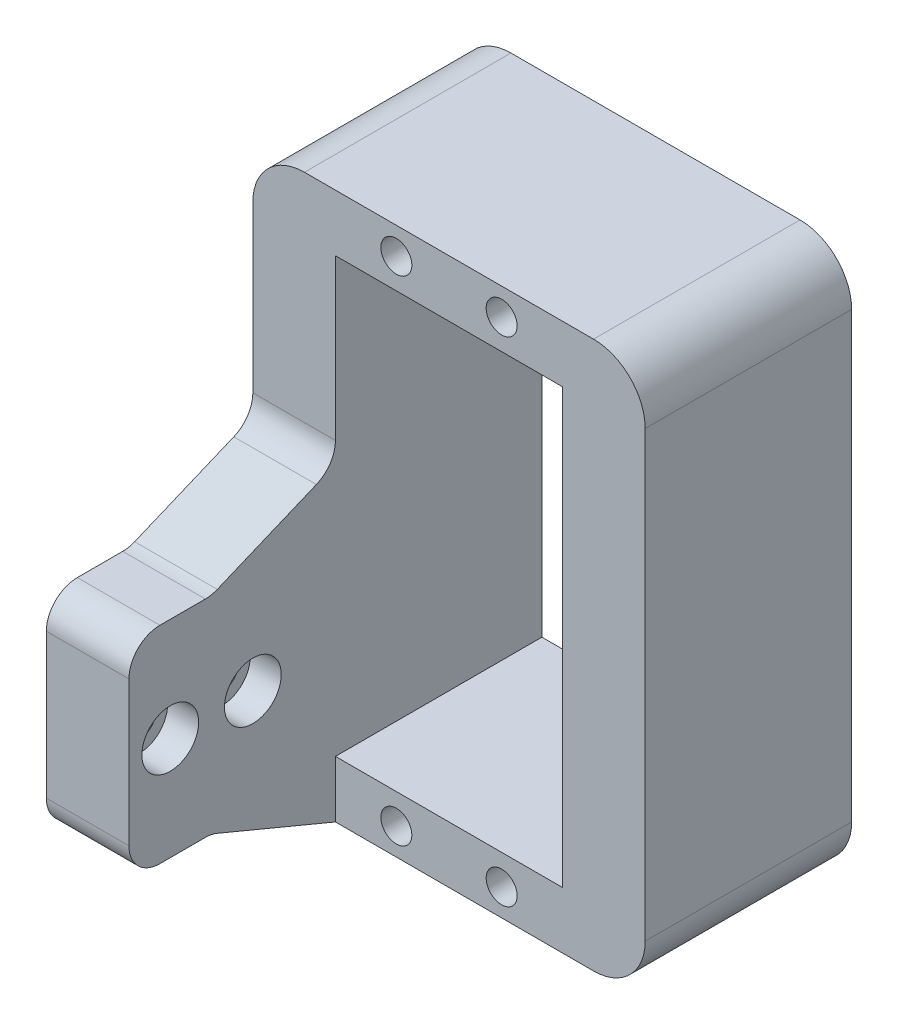
SolidWorks part; units mm, degrees
ref_plane "Front Plane" through (0, 0, 0) normal (0, 0, 1) x (1, 0, 0)
ref_plane "Top Plane" through (0, 0, 0) normal (0, 1, 0) x (1, 0, 0)
ref_plane "Right Plane" through (0, 0, 0) normal (1, 0, 0) x (0, 0, -1)
sketch "Sketch1" plane through (0, 0, 0) normal (0, 0, 1) x (1, 0, 0)
  line L1 (-11, 21) -> (11, 21)
  line L2 (-11, 21) -> (-11, -21)
  line L3 (-11, -21) -> (11, -21)
  line L4 (11, 21) -> (11, -21)
  line L5 (-11, 21) -> (11, -21) construction
  line L6 (-11, -21) -> (11, 21) construction
  line L8 (-19, 26.5) -> (19, 26.5)
  line L9 (-19, 26.5) -> (-19, -26.5)
  line L10 (-19, -26.5) -> (19, -26.5)
  line L11 (19, 26.5) -> (19, -26.5)
  line L12 (-19, 26.5) -> (19, -26.5) construction
  line L13 (-19, -26.5) -> (19, 26.5) construction
  point P0 (0, 0)
  point P6 (0, 0)
  dimension "D1" = 22
  dimension "D2" = 42
  dimension "D4" = 8
  dimension "D3" = 53
extrude "Boss-Extrude1" add sketch "Sketch1" along normal blind 20
sketch "Sketch2" plane through (0, 0, 20) normal (0, 0, 1) x (1, 0, 0)
  line L0 (-19, 26.5) -> (-19, -26.5) construction
  line L1 (-19, -21.5) -> (-11, -21.5)
  line L2 (-19, -21.5) -> (-19, -1.5)
  line L3 (-19, -1.5) -> (-11, -1.5)
  line L4 (-11, -21.5) -> (-11, -1.5)
  line L5 (-11, 21) -> (-11, -21) construction
  line L8 (-19, -26.5) -> (19, -26.5) construction
  point P10 (-15, -21.5)
  dimension "D1" = 20
  dimension "D2" = 5
extrude "Boss-Extrude2" add sketch "Sketch2" along normal blind 20
sketch "Sketch3" plane through (-11, 0, 0) normal (1, 0, 0) x (0, 0, -1)
  line L0 (-40, -21.5) -> (-40, -1.5) construction
  line L1 (-20, -26.5) -> (-20, 26.5) construction
  circle A0 centre (-36, -11.5) radius 2.75
  circle A1 centre (-28, -11.5) radius 2.75
  circle A2 centre (-36, -11.5) radius 1.6
  circle A3 centre (-28, -11.5) radius 1.6
  point P9 (-40, -11.5)
  dimension "D1" = 5.5
  dimension "D4" = 3.2
  dimension "D2" = 4
  dimension "D3" = 8
extrude "Cut-Extrude1" cut sketch "Sketch3" against normal blind 3
extrude "Cut-Extrude2" cut sketch "Sketch3<2>" against normal through all contours A2 | A3 region at (-11, -11.5, 36) region at (-11, -11.5, 28)
sketch "Sketch3<2>" plane through (-11, 0, 0) normal (1, 0, 0) x (0, 0, -1) same geometry as "Sketch3"
sketch "Sketch4" plane through (0, 0, 0) normal (0, 0, -1) x (-1, 0, 0)
  circle A0 centre (-5.1, -23.9) radius 1.5
  circle A1 centre (5.1, -23.9) radius 1.5
  circle A2 centre (-5.1, 23.9) radius 1.5
  circle A3 centre (5.1, 23.9) radius 1.5
  dimension "D1" = 3
extrude "Cut-Extrude3" cut sketch "Sketch4" against normal through all
sketch "Sketch5" plane through (-19, 0, 0) normal (-1, 0, 0) x (0, 0, 1)
  line L0 (20, 26.5) -> (20, -1.5) construction
  line L1 (20, 3.5) -> (32, -1.5)
  line L2 (40, -1.5) -> (20, -1.5) construction
  line L3 (32, -1.5) -> (20, -1.5)
  line L4 (20, -1.5) -> (20, 3.5)
  line L5 (20, -21.5) -> (20, -26.5)
  line L6 (20, -26.5) -> (32, -21.5)
  line L7 (40, -21.5) -> (20, -21.5) construction
  line L8 (32, -21.5) -> (20, -21.5)
  point P12 (31.0704, -21.5)
  dimension "D1" = 12
extrude "Boss-Extrude3" add sketch "Sketch5" against normal up to surface (8 mm away) up to face at (-11, -11.5, 33.25)
fillet "Fillet1" radius 5 4 edges at (-19, -26.5, 10) (19, -26.5, 10) (-19, 26.5, 10) (19, 26.5, 10)
fillet "Fillet2" radius 3 5 edges at (-15, 3.5, 20) (-15, -21.5, 32) (-15, -1.5, 32) (-15, -21.5, 40) (-15, -1.5, 40)
